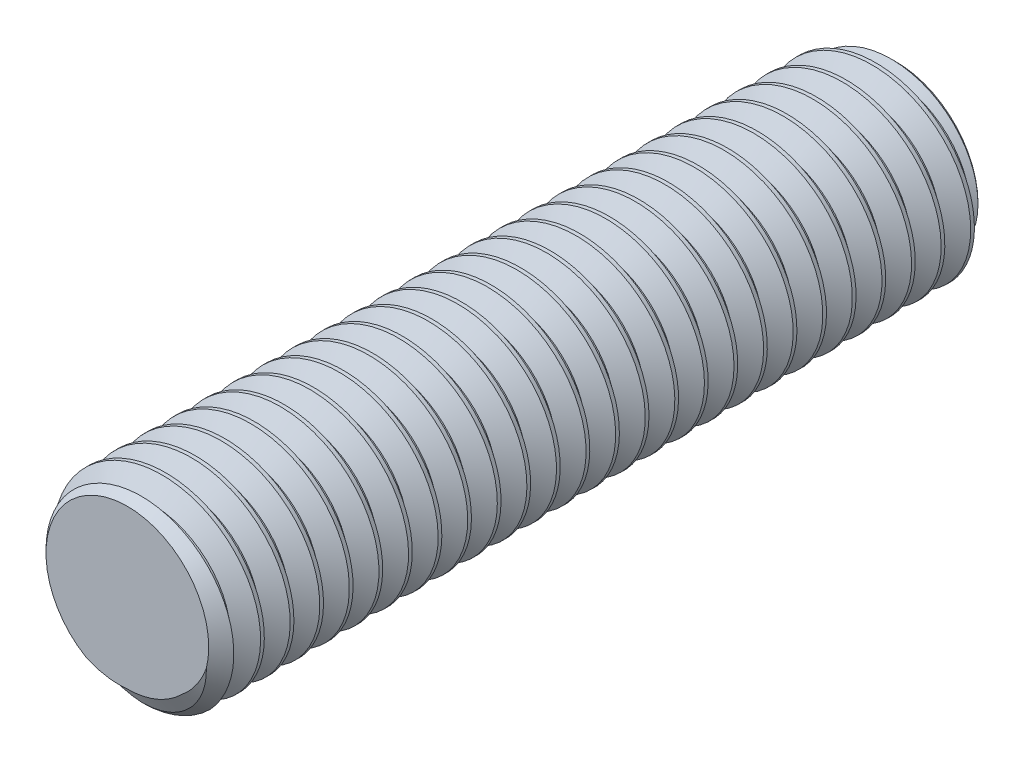
SolidWorks part; units mm, degrees
material "AISI 1020 Steel, Cold Rolled"
ref_plane "Front Plane" through (0, 0, 0) normal (0, 0, 1) x (1, 0, 0)
ref_plane "Top Plane" through (0, 0, 0) normal (0, 1, 0) x (1, 0, 0)
ref_plane "Right Plane" through (0, 0, 0) normal (1, 0, 0) x (0, 0, -1)
sketch "Sketch1" plane through (0, 0, 0) normal (1, 0, 0) x (0, 0, -1)
  line L0 (-25.4, 0) -> (25.4, 0)
  line L1 (-25.4, 6.35) -> (-25.4, -6.35)
  line L5 (-25.4, 6.35) -> (-23.4462, 6.35)
  point P0 (-20.5154, -6.35)
  point P3 (-12.7, 0)
  point P4 (0, 0)
  point P8 (-25.4, 0)
  point P10 (12.7, 0)
  point P11 (25.4, 6.35)
  dimension "Length" = 50.8
  dimension "Thread Diameter" = 12.7
  dimension "Thread Pitch" = 1.9538
  dimension "D2" = 12.7
  dimension "D3" = 12.7
  dimension "D1" = 4.8846
sketch "Sketch2" plane through (0, 0, 0) normal (0, 0, 1) x (1, 0, 0)
  circle A0 centre (0, 0) radius 6.35
  point P3 (-6.35, 0)
  point P5 (6.35, 0)
sketch "Sketch4" plane through (0, 0, 0) normal (0, 0, 1) x (1, 0, 0)
  circle A0 centre (0, 0) radius 6.35 construction
  circle A1 centre (0, 0) radius 6.35
extrude "Boss-Extrude1" add sketch "Sketch4" along normal up to vertex (25.4 mm away) and the other way up to vertex (25.4 mm away) up to point (0, 0, 25.4) other way up to point (0, 0, -25.4)
chamfer "Chamfer1" distance 0.9769 angle 45 2 edges at (6.35, 0, -25.4) (6.35, 0, 25.4)
sketch "Sketch5" plane through (0, 0, 0) normal (1, 0, 0) x (0, 0, -1)
  line L0 (-27.2317, 6.5615) -> (-26.2548, 4.8694) construction
  line L1 (-26.2548, 4.8694) -> (-25.2779, 6.5615) construction
  line L2 (-25.2779, 6.5615) -> (-27.2317, 6.5615) construction
  line L3 (-25.4, 6.35) -> (-23.4462, 6.35) construction
  line L4 (-26.2548, 6.5615) -> (-26.2548, 6.35) construction
  line L5 (-26.2548, 4.8694) -> (-26.2548, 5.0809) construction
  line L6 (-26.3769, 5.0809) -> (-26.1327, 5.0809) construction
  line L7 (-27.1096, 6.35) -> (-25.4, 6.35) construction
  line L8 (-27.1707, 6.4558) -> (-25.3389, 6.4558) construction
  line L9 (-27.1707, 6.4558) -> (-25.3389, 6.4558)
  line L10 (-25.3389, 6.4558) -> (-26.1327, 5.0809)
  line L11 (-26.1327, 5.0809) -> (-26.3769, 5.0809)
  line L12 (-26.3769, 5.0809) -> (-27.1707, 6.4558)
  point P11 (-26.2548, 5.0809)
  point P14 (-26.2548, 6.35)
  point P17 (-26.2548, 6.4558)
  dimension "D1" = 0.2442
sketch "Sketch6" plane through (0, 0, 25.4) normal (0, 0, 1) x (1, 0, 0)
  circle A0 centre (0, 0) radius 6.35
curve "Helix/Spiral1" pitch 1.9538 height 52.7538 turns 27
sweep "Cut-Sweep1" cut profiles "Sketch5" path "Helix/Spiral1"
equation "\"D1@Chamfer1\"=\"Thread Pitch@Sketch1\"*.5"
equation "\"D1@Sketch5\"=\"Thread Pitch@Sketch1\"/8"
equation "\"D3@Helix/Spiral1\"=\"Length@Sketch1\"+\"Thread Pitch@Sketch1\""
equation "\"D4@Helix/Spiral1\"=\"Thread Pitch@Sketch1\""
equation "\"D2@Sketch1\"=\"Thread Diameter@Sketch1\"*1"
equation "\"D1@Sketch1\"=\"Thread Pitch@Sketch1\"*2.5"
equation "\"D3@Sketch1\"=\"D2@Sketch1\""
